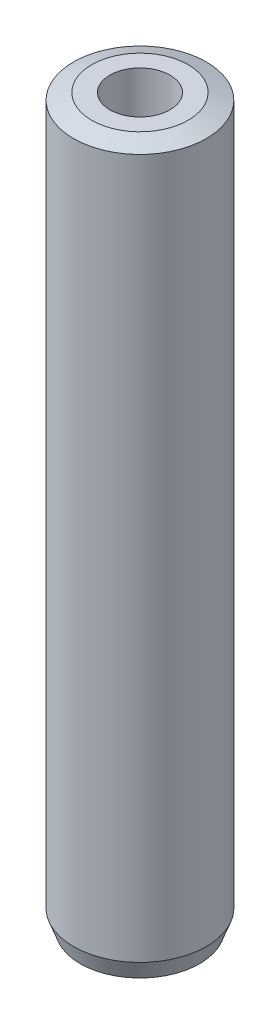
SolidWorks part; units mm, degrees
ref_plane "Front Plane" through (0, 0, 0) normal (0, 0, 1) x (1, 0, 0)
ref_plane "Top Plane" through (0, 0, 0) normal (0, 1, 0) x (1, 0, 0)
ref_plane "Right Plane" through (0, 0, 0) normal (1, 0, 0) x (0, 0, -1)
sketch "Sketch1" plane through (0, 0, 0) normal (0, 1, 0) x (1, 0, 0)
  circle A0 centre (0, 0) radius 55
  dimension "SHAFT_OD" = 110
extrude "Boss-Extrude1" add sketch "Sketch1" along normal blind 600
sketch "Sketch2" plane through (0, 0, 0) normal (0, 1, 0) x (1, 0, 0)
  circle A0 centre (0, 0) radius 24.9073
  dimension "BORE_D" = 49.8146
extrude "Cut-Extrude1" cut sketch "Sketch2" along normal through all
chamfer "Chamfer1" distance 5.5658 angle 69.768 2 edges at (0, 600, 55) (0, 0, 55) first distance on face at (0, 600, 55) first distance on face at (0, 0, 24.9073)
